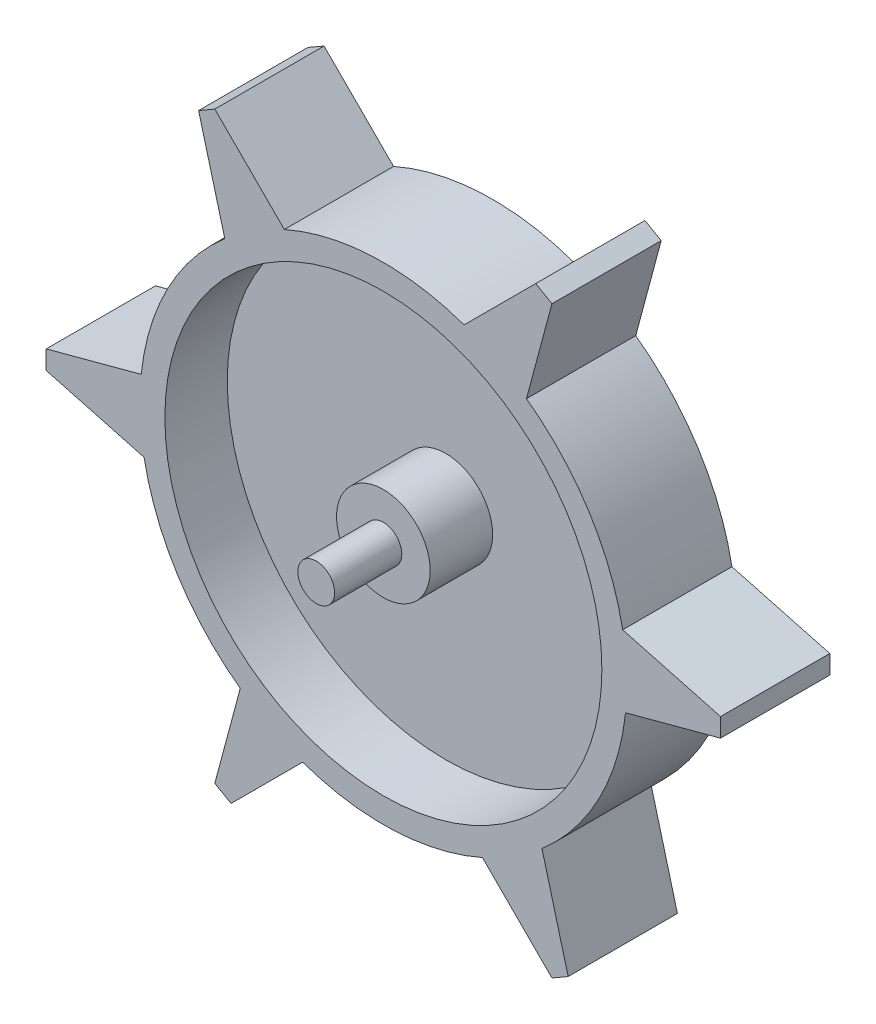
SolidWorks part; units mm, degrees
ref_plane "Front Plane" through (0, 0, 0) normal (0, 0, 1) x (1, 0, 0)
ref_plane "Top Plane" through (0, 0, 0) normal (0, 1, 0) x (1, 0, 0)
ref_plane "Right Plane" through (0, 0, 0) normal (1, 0, 0) x (0, 0, -1)
sketch "Sketch1" plane through (0, 0, 0) normal (0, 0, 1) x (1, 0, 0)
  line L0 (-54, -3) -> (-38.3298, -7.1988)
  line L1 (-54, 0) -> (-54, -3)
  line L21 (-54, 0) -> (-38.7864, 4.0765)
  circle A0 centre (0, 0) radius 39
  point P34 (0, 0)
  dimension "D1" = 78
  dimension "D2" = 15
  dimension "D3" = 3
  dimension "D5" = 15
extrude "Boss-Extrude1" add sketch "Sketch1" along normal blind 17.5 contours A0 | A0 L1 | A0 | A0 | A0 | A0 | A0 | A0 region at (-44.962, -1.5432, 0) region at (0, 0, 0)
sketch "Sketch3" plane through (0, 0, 17.5) normal (0, 0, 1) x (1, 0, 0)
  circle A0 centre (0, 0) radius 2.95
  dimension "D1" = 5.9
extrude "Boss-Extrude5" add sketch "Sketch3" along direction (0, 0, 1) on the side against the normal blind 28.25 and the other way blind 10.75
sketch "Sketch2" plane through (0, 0, 0) normal (0, 0, -1) x (-1, 0, 0)
  line L1 (-1.2238, -1.18) -> (1.2238, -1.18)
  arc A0 (1.2238, -1.18) -> (-1.2238, -1.18) centre (0, 0) ccw
  dimension "D1" = 3.4
  dimension "D2" = 1.18
extrude "Cut-Extrude1" cut sketch "Sketch2" against normal blind 7.5 from surface starting at face at (2.95, 0, -10.75)
pattern_circular "CirPattern1" count 6 over 360 about axis through (0, 0, 17.5) along (0, 0, 1) of "Boss-Extrude1"
sketch "Sketch4" plane through (0, 0, 17.5) normal (0, 0, 1) x (1, 0, 0)
  circle A0 centre (0, 0) radius 35
  circle A1 centre (0, 0) radius 7.5
  dimension "D1" = 70
  dimension "D2" = 15
extrude "Cut-Extrude2" cut sketch "Sketch4" against normal blind 10
